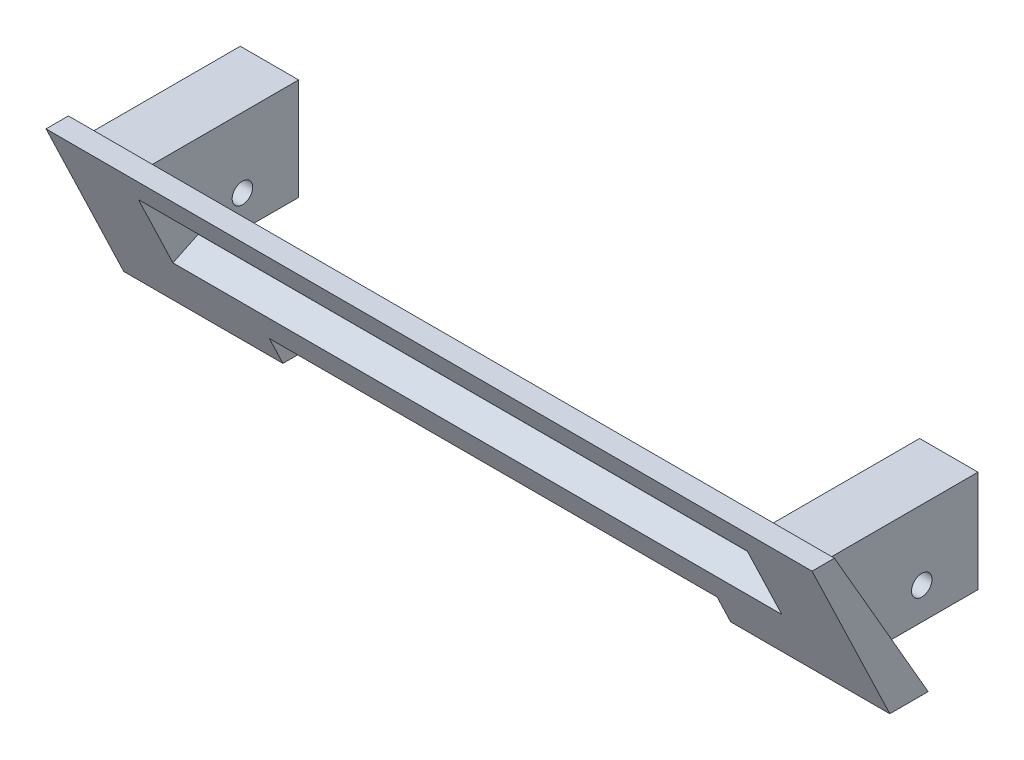
SolidWorks part; units mm, degrees
ref_plane "Front Plane" through (0, 0, 0) normal (0, 0, 1) x (1, 0, 0)
ref_plane "Top Plane" through (0, 0, 0) normal (0, 1, 0) x (1, 0, 0)
ref_plane "Right Plane" through (0, 0, 0) normal (1, 0, 0) x (0, 0, -1)
sketch "Sketch1" plane through (0, 0, 0) normal (1, 0, 0) x (0, 0, -1)
  line L0 (0, 0) -> (-29.3294, 50.8)
  line L1 (0, 0) -> (50, 0) construction
  line L2 (-29.3294, 50.8) -> (-36.3294, 50.8)
  line L3 (-36.3294, 50.8) -> (-12, 0)
  line L7 (-12, 0) -> (0, 0)
  dimension "D1" = 12
  dimension "D2" = 60
  dimension "D3" = 50.8
  dimension "D4" = 7
extrude "Boss-Extrude2" add sketch "Sketch1" along normal mid plane 239.55
sketch "Sketch2" plane through (0, 0, 0) normal (0, 0, 1) x (1, 0, 0)
  line L0 (0, 0) -> (0, 50.8) construction
  line L5 (115.75, 47.625) -> (96.7, 47.625) construction
  line L6 (115.75, 47.625) -> (115.75, 15) construction
  line L11 (115.75, 15) -> (96.7, 15) construction
  line L12 (96.7, 47.625) -> (96.7, 15) construction
  line L13 (119.775, 0) -> (-119.775, 0) construction
  line L14 (115.35, 47.225) -> (115.35, 15.4)
  line L15 (115.35, 15.4) -> (97.1, 15.4)
  line L28 (97.1, 47.225) -> (97.1, 15.4)
  line L29 (115.35, 47.225) -> (97.1, 47.225)
  line L30 (-96.7, 47.625) -> (-96.7, 15) construction
  line L31 (-115.75, 15) -> (-96.7, 15) construction
  line L32 (-115.75, 47.625) -> (-115.75, 15) construction
  line L33 (-115.75, 47.625) -> (-96.7, 47.625) construction
  line L34 (-115.35, 47.225) -> (-97.1, 47.225)
  line L35 (-97.1, 47.225) -> (-97.1, 15.4)
  line L36 (-115.35, 15.4) -> (-97.1, 15.4)
  line L37 (-115.35, 47.225) -> (-115.35, 15.4)
  line L40 (119.775, 50.8) -> (-119.775, 50.8) construction
  line L41 (119.775, 0) -> (119.775, 50.8) construction
  dimension "D2" = 19.05
  dimension "D4" = 3.175
  dimension "D7" = 4.025
  dimension "D1" = 193.4
  dimension "D3" = 15
  dimension "D5" = 0.4
extrude "Boss-Extrude1" add sketch "Sketch2" along normal up to surface and the other way blind 20 up to face at (0, 25.4, 14.6647)
sketch "Sketch12" plane through (0, -4.6748, 9.7611) normal (0, -0.4319, 0.9019) x (1, 0, 0)
  line L0 (-95.2, -286.6937) -> (-95.2, 1.1513) construction
  line L1 (-95.2, -286.6937) -> (-95.2, 1.1513) construction
  line L2 (119.775, 0) -> (-119.775, 0) construction
  line L3 (70, 15) -> (-70, 15)
  line L4 (70, 15) -> (70, 0)
  line L5 (70, 0) -> (-70, 0)
  line L6 (-70, 15) -> (-70, 0)
  line L7 (70, 15) -> (-70, 0) construction
  line L8 (70, 0) -> (-70, 15) construction
  line L10 (95.2, 51.5088) -> (-95.2, 51.5088)
  line L11 (95.2, 51.5088) -> (95.2, 26.5088)
  line L12 (95.2, 26.5088) -> (-95.2, 26.5088)
  line L13 (-95.2, 51.5088) -> (-95.2, 26.5088)
  line L14 (95.2, 51.5088) -> (-95.2, 26.5088) construction
  line L15 (95.2, 26.5088) -> (-95.2, 51.5088) construction
  line L16 (-120.6, 61.5088) -> (120.6, 61.5088) construction
  point P2 (0, 7.5)
  point P11 (0, 39.0088)
  dimension "D1" = 15
  dimension "D2" = 140
  dimension "D3" = 10
  dimension "D4" = 25
  dimension "D5" = 11.5088
extrude "Cut-Extrude4" cut sketch "Sketch12" against normal up to next
hole_wizard "M6 Clearance Hole1" positions "Sketch11" profile "Sketch10" hole size "M6" standard "ANSI Metric" end condition through all
sketch "Sketch11" plane through (115.35, 0, 0) normal (1, 0, 0) x (0, 0, -1)
  point P0 (2.4206, 25.4)
sketch "Sketch10" plane through (115.35, 25.4, -2.4206) normal (0, 1, 0) x (0, 0, -1)
  line L0 (0, 0) -> (0, 235.125)
  line L1 (0, 235.125) -> (3.2, 235.125)
  line L2 (3.2, 235.125) -> (3.2, 0)
  line L5 (3.2, 0) -> (0, 0)
  line L11 (0, -6.35) -> (0, 107.95) construction
  dimension "Thru Hole Dia." = 6.4
  dimension "Thru Hole Depth" = 235.125
equation "\"D1@Sketch2\"=187.05mm+0.25in"
equation "\"RailSpacing\"= 188.75mm"
equation "\"D1@Boss-Extrude2\"=\"RailSpacing\"+2in"
